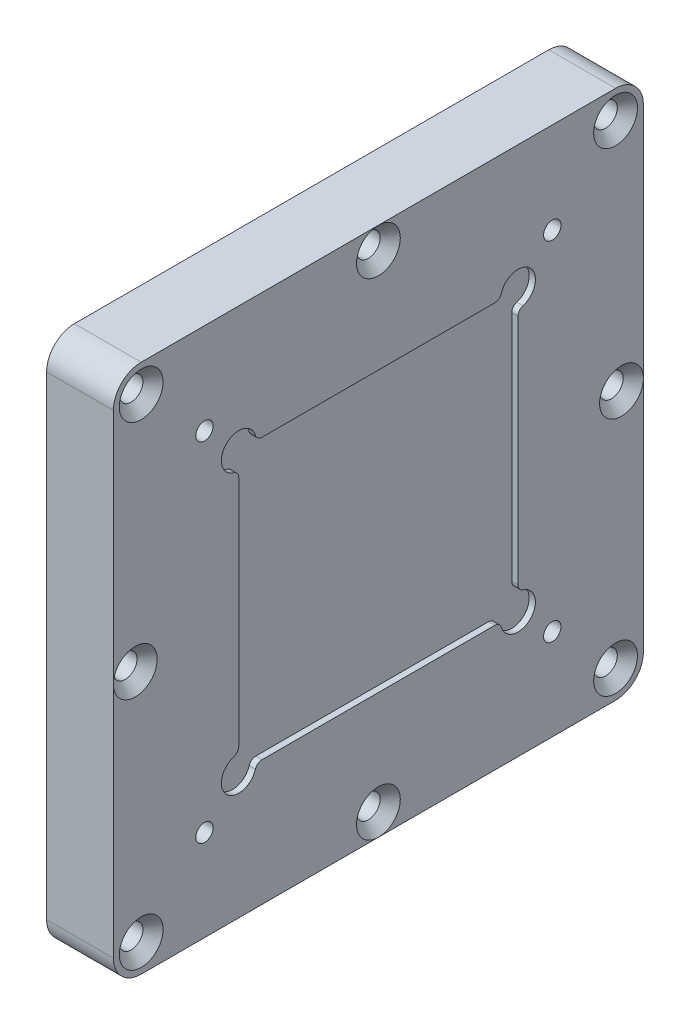
SolidWorks part; units mm, degrees
ref_plane "Front Plane" through (0, 0, 0) normal (0, 0, 1) x (1, 0, 0)
ref_plane "Top Plane" through (0, 0, 0) normal (0, 1, 0) x (1, 0, 0)
ref_plane "Right Plane" through (0, 0, 0) normal (1, 0, 0) x (0, 0, -1)
sketch "Sketch2" plane through (0, 0, 0) normal (1, 0, 0) x (0, 0, -1)
  line L1 (-34.1, -38.1) -> (34.1, -38.1)
  line L2 (-38.1, -34.1) -> (-38.1, 34.1)
  line L3 (-34.1, 38.1) -> (34.1, 38.1)
  line L4 (38.1, -34.1) -> (38.1, 34.1)
  line L5 (-38.1, -38.1) -> (38.1, 38.1) construction
  line L6 (-38.1, 38.1) -> (38.1, -38.1) construction
  arc A0 (-34.1, -38.1) -> (-38.1, -34.1) centre (-34.1, -34.1) cw
  arc A1 (34.1, -38.1) -> (38.1, -34.1) centre (34.1, -34.1) ccw
  arc A2 (34.1, 38.1) -> (38.1, 34.1) centre (34.1, 34.1) cw
  arc A3 (-38.1, 34.1) -> (-34.1, 38.1) centre (-34.1, 34.1) cw
  point P0 (0, 0)
  dimension "D3" = 4
  dimension "D1" = 76.2
  dimension "D2" = 76.2
extrude "Boss-Extrude1" add sketch "Sketch2" along normal blind 9.6
sketch "Sketch21" plane through (9.6, 0, 0) normal (-1, 0, 0) x (0, 0, 1)
  line L0 (-34.1, 34.1) -> (-34.1, -34.1) construction
  line L1 (-34.1, -34.1) -> (34.1, -34.1) construction
  line L2 (-38.1, -34.1) -> (-38.1, 34.1) construction
  line L3 (-34.1, 38.1) -> (34.1, 38.1) construction
  line L4 (38.1, 34.1) -> (38.1, -34.1) construction
  line L5 (34.1, -38.1) -> (-34.1, -38.1) construction
  line L6 (34.1, -34.1) -> (34.1, 34.1) construction
  line L7 (34.1, 34.1) -> (-34.1, 34.1) construction
  dimension "D1" = 4
  dimension "D2" = 4
  dimension "D3" = 4
  dimension "D4" = 4
sketch "Sketch24" plane through (9.6, 0, 0) normal (1, 0, 0) x (0, 0, -1)
  line L1 (20.075, -20.075) -> (-20.075, -20.075)
  line L2 (20.075, -20.075) -> (20.075, 20.075)
  line L3 (20.075, 20.075) -> (-20.075, 20.075)
  line L4 (-20.075, -20.075) -> (-20.075, 20.075)
  line L5 (20.075, -20.075) -> (-20.075, 20.075) construction
  line L6 (20.075, 20.075) -> (-20.075, -20.075) construction
  circle A0 centre (-20.075, 20.075) radius 2.5
  circle A1 centre (20.075, 20.075) radius 2.5
  circle A2 centre (20.075, -20.075) radius 2.5
  circle A3 centre (-20.075, -20.075) radius 2.5
  point P0 (0, 0)
  dimension "D3" = 5
  dimension "D4" = 5
  dimension "D5" = 5
  dimension "D6" = 5
  dimension "D1" = 40.15
  dimension "D2" = 40.15
extrude "Cut-Extrude1" cut sketch "Sketch24" against normal blind 0.9 contours A3 L1 A2 L2 A1 L3 A0 L4 | L3 A0 L4 | L4 A0 L3 | L3 A1 L2 | L2 A1 L3 | L1 A2 L2 | L2 A2 L1 | L4 A3 L1 | L1 L4 L3 L2 region at (9.6, -20.4287, 20.4287) region at (9.6, 0, 0) region at (9.6, -19.014, -19.014) region at (9.6, -20.4287, -20.4287) region at (9.6, 20.4287, 20.4287) region at (9.6, 19.014, 19.014) region at (9.6, 19.014, -19.014) region at (9.6, 20.4287, -20.4287)
fillet "Fillet1" radius 1 8 edges at (9.15, -20.075, 17.575) (9.15, -17.575, 20.075) (9.15, -17.575, -20.075) (9.15, -20.075, -17.575) (9.15, 17.575, -20.075) (9.15, 20.075, -17.575) (9.15, 20.075, 17.575) (9.15, 17.575, 20.075)
sketch "Sketch33" plane through (0, 0, 0) normal (-1, 0, 0) x (0, 0, 1)
  line L0 (-36.9284, 36.9284) -> (36.9284, -36.9284) construction
  circle A0 centre (0, 0) radius 5
  arc A1 (34.1, -38.1) -> (38.1, -34.1) centre (34.1, -34.1) ccw construction
  arc A2 (-34.1, 38.1) -> (-38.1, 34.1) centre (-34.1, 34.1) ccw construction
  point P3 (-3.5355, 3.5355)
  point P4 (3.5355, -3.5355)
  point P5 (-3.5355, -3.5355)
  point P6 (3.5355, 3.5355)
  dimension "D1" = 10
curve "Helix/Spiral1" [suppressed]
sketch "Sketch36" plane through (0, 0, 0) normal (0, 0, 1) x (1, 0, 0)
  line L1 (-6, -1.75) -> (6, -1.75)
  line L2 (-6, -1.75) -> (-6, 1.75)
  line L3 (-6, 1.75) -> (6, 1.75)
  line L4 (6, -1.75) -> (6, 1.75)
  line L5 (-6, -1.75) -> (6, 1.75) construction
  line L6 (-6, 1.75) -> (6, -1.75) construction
  point P0 (0, 0)
  dimension "D1" = 12
  dimension "D2" = 3.5
sweep "Cut-Sweep1" [suppressed] cut profiles "Sketch36" path "Helix/Spiral1"
ref_axis "Axis1" [suppressed] through (10.08, 0, 0) along (-1, 0, 0)
pattern_circular "CirPattern1" [suppressed] count 14 every 30 about axis through (10.08, 0, 0) along (-1, 0, 0) of bodies 119
hole_wizard "CSK for M3 Flat Head Machine Screw1" positions "Sketch22" profile "Sketch23" countersink size "M3" standard "ANSI Metric" end condition through all
sketch "Sketch22" plane through (9.6, 0, 0) normal (-1, 0, 0) x (0, 0, 1)
  line L0 (38.1, 34.1) -> (38.1, -34.1) construction
  line L1 (-38.1, -34.1) -> (-38.1, 34.1) construction
  line L3 (34.1, -38.1) -> (-34.1, -38.1) construction
  line L4 (-34.1, 38.1) -> (34.1, 38.1) construction
  point P0 (-34.1, 34.1)
  point P3 (34.1, 34.1)
  point P6 (34.1, -34.1)
  point P9 (-34.1, -34.1)
  point P12 (0, 34.95)
  point P14 (34.95, 0)
  point P16 (0, -34.95)
  point P18 (-34.95, 0)
  dimension "D1" = 3.15
  dimension "D2" = 3.15
  dimension "D3" = 3.15
  dimension "D4" = 3.15
sketch "Sketch23" plane through (9.6, 34.1, -34.1) normal (0, 1, 0) x (0, 0, -1)
  line L0 (0, 0) -> (0, 9.6)
  line L1 (0, 9.6) -> (1.7, 9.6)
  line L2 (1.7, 9.6) -> (1.7, 1.45)
  line L3 (1.7, 1.45) -> (3.15, 0)
  line L5 (3.15, 0) -> (0, 0)
  line L6 (-1.7, 1.45) -> (-3.15, 0) construction
  line L11 (0, -6.35) -> (0, 107.95) construction
  dimension "Thru Hole Dia." = 3.4
  dimension "Thru Hole Depth" = 9.6
  dimension "Near C'Sink Dia." = 6.3
  dimension "Near C'Sink Angle" = 90
hole_wizard "M3x0.5 Tapped Hole1" positions "Sketch27" profile "Sketch26" tap size "M3x0.5" standard "ANSI Metric"
sketch "Sketch27" plane through (9.6, 0, 0) normal (1, 0, 0) x (0, 0, -1)
  line L0 (-25, 25) -> (25, -25) construction
  line L2 (-25, -25) -> (25, 25) construction
  point P0 (-25, 25)
  point P2 (25, 25)
  point P4 (25, -25)
  point P6 (-25, -25)
  point P21 (0, 0)
  dimension "D1" = 50
  dimension "D2" = 50
sketch "Sketch26" plane through (9.6, 25, 25) normal (0, 1, 0) x (0, 0, -1)
  line L0 (0, 0) -> (0, 8.3711)
  line L1 (0, 8.3711) -> (1.25, 7.62)
  line L2 (1.25, 7.62) -> (1.25, 0)
  line L5 (1.25, 0) -> (0, 0)
  line L10 (0, 8.3711) -> (-1.25, 7.62) construction
  line L11 (0, -6.35) -> (0, 107.95) construction
  dimension "Tap Drill Dia." = 2.5
  dimension "Tap Drill Depth" = 7.62
  dimension "Drill Angle" = 118
hole_wizard "M3x0.5 Tapped Hole2" positions "Sketch31" profile "Sketch30" tap size "M3x0.5" standard "ANSI Metric"
sketch "Sketch31" plane through (0, 0, 0) normal (-1, 0, 0) x (0, 0, 1)
  point P0 (-16, 16)
  point P2 (16, 16)
  point P4 (16, -16)
  point P6 (-16, -16)
  dimension "D1" = 32
  dimension "D2" = 32
  dimension "D3" = 16
  dimension "D4" = 16
sketch "Sketch30" plane through (0, 16, -16) normal (0, 1, 0) x (0, 0, 1)
  line L0 (0, 0) -> (0, 5.8311)
  line L1 (0, 5.8311) -> (1.25, 5.08)
  line L2 (1.25, 5.08) -> (1.25, 0)
  line L5 (1.25, 0) -> (0, 0)
  line L10 (0, 5.8311) -> (-1.25, 5.08) construction
  line L11 (0, -6.35) -> (0, 107.95) construction
  dimension "Tap Drill Dia." = 2.5
  dimension "Tap Drill Depth" = 5.08
  dimension "Drill Angle" = 118
sketch "Sketch37" plane through (0, 0, 0) normal (-1, 0, 0) x (0, 0, 1)
  line L0 (-1.75, 1.75) -> (-1.75, 25.4)
  line L1 (-1.75, 1.75) -> (-25.4, 1.75)
  line L2 (-1.75, -1.75) -> (-25.4, -1.75)
  line L3 (-1.75, -1.75) -> (-1.75, -25.4)
  line L4 (1.75, -25.4) -> (1.75, -1.75)
  line L5 (1.75, -1.75) -> (25.4, -1.75)
  line L6 (1.75, 25.4) -> (1.75, 1.75)
  line L7 (1.75, 1.75) -> (25.4, 1.75)
  line L8 (34.1, -38.1) -> (-34.1, -38.1) construction
  line L9 (-2.75, -2.75) -> (-2.75, -25.4)
  line L10 (-2.75, -2.75) -> (-25.4, -2.75)
  line L11 (-2.75, 2.75) -> (-2.75, 25.4)
  line L12 (-2.75, 2.75) -> (-25.4, 2.75)
  line L13 (2.75, 25.4) -> (2.75, 2.75)
  line L14 (2.75, 2.75) -> (25.4, 2.75)
  line L15 (2.75, -25.4) -> (2.75, -2.75)
  line L16 (2.75, -2.75) -> (25.4, -2.75)
  line L17 (-6.75, -6.75) -> (-6.75, -25.4)
  line L18 (-6.75, -6.75) -> (-25.4, -6.75)
  line L19 (-11.75, 11.75) -> (-25.4, 11.75)
  line L20 (-11.75, 11.75) -> (-11.75, 25.4)
  line L21 (11.75, 25.4) -> (11.75, 11.75)
  line L22 (11.75, 11.75) -> (25.4, 11.75)
  line L23 (-6.75, 6.75) -> (-6.75, 25.4)
  line L24 (-6.75, 6.75) -> (-25.4, 6.75)
  line L25 (6.75, 25.4) -> (6.75, 6.75)
  line L26 (6.75, 6.75) -> (25.4, 6.75)
  line L27 (34.1, -34.1) -> (34.1, 34.1)
  line L28 (34.1, 34.1) -> (-34.1, 34.1)
  line L29 (-34.1, 34.1) -> (-34.1, -34.1)
  line L30 (-34.1, -34.1) -> (34.1, -34.1)
  line L31 (34.1, -34.1) -> (34.1, 34.1)
  line L32 (34.1, 34.1) -> (-34.1, 34.1)
  line L33 (-34.1, 34.1) -> (-34.1, -34.1)
  line L34 (-34.1, -34.1) -> (34.1, -34.1)
  line L35 (6.75, -25.4) -> (6.75, -6.75)
  line L36 (6.75, -6.75) -> (25.4, -6.75)
  line L37 (-7.75, -7.75) -> (-7.75, -25.4)
  line L38 (-7.75, -7.75) -> (-25.4, -7.75)
  line L39 (-7.75, 7.75) -> (-7.75, 25.4)
  line L40 (-7.75, 7.75) -> (-25.4, 7.75)
  line L41 (7.75, 25.4) -> (7.75, 7.75)
  line L42 (7.75, 7.75) -> (25.4, 7.75)
  line L43 (7.75, -25.4) -> (7.75, -7.75)
  line L44 (7.75, -7.75) -> (25.4, -7.75)
  line L45 (-11.75, -11.75) -> (-11.75, -25.4)
  line L46 (-11.75, -11.75) -> (-25.4, -11.75)
  line L47 (-25.4, 12.75) -> (-19.75, 12.75)
  line L48 (25.4, -25.4) -> (-25.4, -25.4)
  line L49 (25.4, -25.4) -> (25.4, 25.4)
  line L50 (25.4, 25.4) -> (-25.4, 25.4)
  line L51 (-25.4, -25.4) -> (-25.4, 25.4)
  line L52 (25.4, -25.4) -> (-25.4, 25.4) construction
  line L53 (25.4, 25.4) -> (-25.4, -25.4) construction
  line L54 (-19.75, 12.75) -> (-19.75, 19.75)
  line L55 (-19.75, 19.75) -> (-12.75, 19.75)
  line L56 (-12.75, 19.75) -> (-12.75, 25.4)
  line L57 (12.75, 25.4) -> (12.75, 19.75)
  line L58 (12.75, 19.75) -> (19.75, 19.75)
  line L59 (19.75, 19.75) -> (19.75, 12.75)
  line L60 (19.75, 12.75) -> (25.4, 12.75)
  line L61 (-25.4, -12.75) -> (-19.75, -12.75)
  line L62 (-19.75, -12.75) -> (-19.75, -19.75)
  line L63 (-19.75, -19.75) -> (-12.75, -19.75)
  line L64 (-12.75, -19.75) -> (-12.75, -25.4)
  line L65 (12.75, -25.4) -> (12.75, -19.75)
  line L66 (12.75, -19.75) -> (19.75, -19.75)
  line L67 (19.75, -19.75) -> (19.75, -12.75)
  line L68 (19.75, -12.75) -> (25.4, -12.75)
  line L69 (11.75, -25.4) -> (11.75, -11.75)
  line L70 (11.75, -11.75) -> (25.4, -11.75)
  line L71 (-20.4503, -25.4) -> (-25.4, -20.4503)
  line L72 (-25.4, 20.4503) -> (-20.4503, 25.4)
  line L73 (20.4503, 25.4) -> (25.4, 20.4503)
  line L74 (20.4503, -25.4) -> (25.4, -20.4503)
  point P0 (0, 0)
  dimension "D1" = 1.75
  dimension "D2" = 1.75
  dimension "D3" = 1.75
  dimension "D4" = 1.75
  dimension "D9" = 23.65
  dimension "D23" = 1
  dimension "D24" = 7
  dimension "D25" = 7
  dimension "D5" = 1
  dimension "D6" = 1
  dimension "D7" = 1
  dimension "D8" = 1
  dimension "D10" = 4
  dimension "D11" = 4
  dimension "D12" = 4
  dimension "D13" = 4
  dimension "D14" = 4
  dimension "D15" = 1
  dimension "D16" = 1
  dimension "D17" = 1
  dimension "D18" = 1
  dimension "D19" = 4
  dimension "D20" = 4
  dimension "D21" = 4
  dimension "D22" = 4
extrude "Cut-Extrude2" cut sketch "Sketch37" against normal blind 6 contours L72 L51 L47 L54 L55 L56 L50 | L71 L48 L64 L63 L62 L61 L51 | L48 L74 L49 L68 L67 L66 L65 | L73 L50 L57 L58 L59 L60 L49 | L21 L50 L41 L42 L49 L22 | L25 L50 L13 L14 L49 L26 | L51 L2 L3 L48 L4 L5 L49 L7 L6 L50 L0 L1 | L51 L12 L11 L50 L23 L24 | L51 L40 L39 L50 L20 L19 | L51 L18 L17 L48 L9 L10 | L51 L46 L45 L48 L37 L38 | L36 L49 L16 L15 L48 L35 | L69 L70 L49 L44 L43 L48 region at (0, 0, 0) region at (0, 14.075, -3.0703) region at (0, 25.0797, 4.75) region at (0, -3.0703, -14.075) region at (0, 16.575, -7.9996) region at (0, 25.1504, 9.75) region at (0, -7.9996, -16.575) region at (0, -4.75, 25.0797) region at (0, 19.8966, -19.8966) region at (0, 19.8966, 19.8966) region at (0, -19.8966, -19.8966) region at (0, -9.75, 25.1504) region at (0, -19.8966, 19.8966)
chamfer "Chamfer1" distance 4 angle 45 20 edges at (6, 9.75, -25.4) (6, 4.75, -25.4) (6, 0, -25.4) (6, -4.75, -25.4) (6, -9.75, -25.4) (6, -25.4, -9.75) (6, -25.4, -4.75) (6, -25.4, 0) (6, -25.4, 4.75) (6, -25.4, 9.75) (6, -9.75, 25.4) (6, -4.75, 25.4) (6, 0, 25.4) (6, 4.75, 25.4) (6, 9.75, 25.4) (6, 25.4, 9.75) (6, 25.4, 4.75) (6, 25.4, 0) (6, 25.4, -4.75) (6, 25.4, -9.75)
fillet "Fillet2" radius 1.6 126 edges at (1, 25.4, -7.75) (4, 23.4, -7.75) (4, 23.4, -2.75) (1, 25.4, -2.75) (1, 25.4, 1.75) (4, 23.4, 1.75) (4, 23.4, 6.75) (1, 25.4, 6.75) (1, 25.4, 11.75) (4, 23.4, 11.75) (4, 23.4, 7.75) (1, 25.4, 7.75) (4, 23.4, 2.75) (1, 25.4, 2.75) (4, 23.4, -1.75) (1, 25.4, -1.75) (4, 23.4, -6.75) (1, 25.4, -6.75) (4, 23.4, -11.75) (1, 25.4, -11.75) (3, 20.4503, 25.4) (3, 25.4, 20.4503) (3, 25.4, 12.75) (3, 19.75, 12.75) (3, -19.75, -12.75) (3, -12.75, 19.75) (3, -19.75, 12.75) (3, -25.4, 12.75) (3, -25.4, 20.4503) (3, -20.4503, 25.4) (3, -12.75, 25.4) (4, -6.75, 23.4) (1, -6.75, 25.4) (4, -1.75, 23.4) (1, -1.75, 25.4) (4, 2.75, 23.4) (1, 2.75, 25.4) (4, 7.75, 23.4) (1, 7.75, 25.4) (3, 12.75, 25.4) (4, 11.75, 23.4) (1, 11.75, 25.4) (4, 6.75, 23.4) (1, 6.75, 25.4) (4, 1.75, 23.4) (1, 1.75, 25.4) (4, -2.75, 23.4) (1, -2.75, 25.4) (4, -7.75, 23.4) (1, -7.75, 25.4) (4, -11.75, 23.4) (1, -11.75, 25.4) (1, -25.4, 11.75) (4, -23.4, 11.75) (1, -25.4, 7.75) (4, -23.4, 7.75) (1, -25.4, 6.75) (4, -23.4, 6.75) (1, -25.4, 2.75) (4, -23.4, 2.75) (3, -25.4, -12.75) (3, -25.4, -20.4503) (3, -20.4503, -25.4) (3, -12.75, -25.4) (3, -12.75, -19.75) (3, 12.75, -19.75) (3, 19.75, -12.75) (3, 25.4, -12.75) (3, 25.4, -20.4503) (3, 20.4503, -25.4) (3, 12.75, -25.4) (4, 7.75, -23.4) (1, 7.75, -25.4) (4, 2.75, -23.4) (1, 2.75, -25.4) (1, -1.75, -25.4) (4, -1.75, -23.4) (4, -7.75, -23.4) (4, -2.75, -23.4) (4, 1.75, -23.4) (4, 6.75, -23.4) (4, 11.75, -23.4) (1, 11.75, -25.4) (1, 6.75, -25.4) (1, 1.75, -25.4) (1, -2.75, -25.4) (1, -7.75, -25.4) (1, -11.75, -25.4) (4, -11.75, -23.4) (4, -23.4, -7.75) (4, -23.4, -11.75) (4, -23.4, -6.75) (4, -23.4, -2.75) (4, -23.4, 1.75) (4, -23.4, -1.75) (1, -25.4, -1.75) (1, -25.4, 1.75) (1, -25.4, -2.75) (1, -25.4, -6.75) (1, -25.4, -7.75) (1, -25.4, -11.75) (3, -19.75, -19.75) (3, -11.75, -11.75) (3, -6.75, -6.75) (3, -7.75, -7.75) (3, -2.75, -2.75) (3, 19.75, -19.75) (3, 11.75, -11.75) (3, 7.75, -7.75) (3, 2.75, -2.75) (3, 1.75, 1.75) (3, 6.75, 6.75) (3, 11.75, 11.75) (3, 19.75, 19.75) (3, 7.75, 7.75) (3, 2.75, 2.75) (3, 1.75, -1.75) (3, -1.75, -1.75) (3, -19.75, 19.75) (3, -11.75, 11.75) (3, -7.75, 7.75) (3, -6.75, 6.75) (3, -1.75, 1.75) (3, -2.75, 2.75) (4, -6.75, -23.4) (1, -6.75, -25.4)
